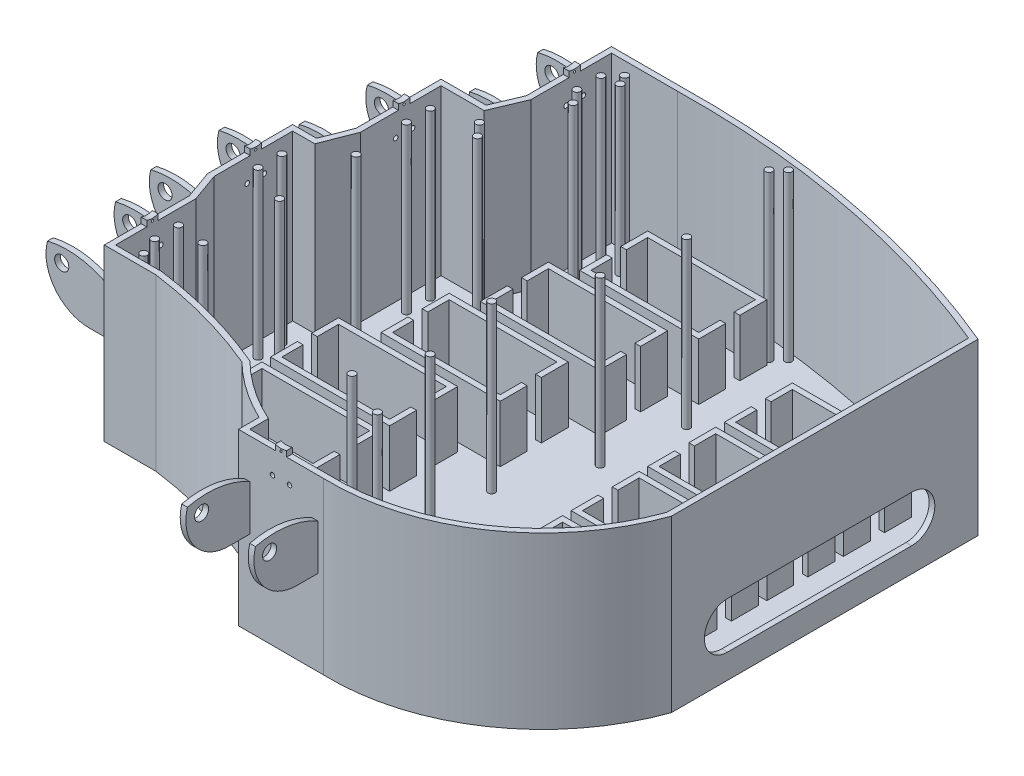
SolidWorks part; units mm, degrees
ref_plane "Front Plane" through (0, 0, 0) normal (0, 0, 1) x (1, 0, 0)
ref_plane "Top Plane" through (0, 0, 0) normal (0, 1, 0) x (1, 0, 0)
ref_plane "Right Plane" through (0, 0, 0) normal (1, 0, 0) x (0, 0, -1)
ref_plane "Palm Side Plane" through (0, 38.1, 0) normal (0, 1, 0) x (1, 0, 0)
ref_plane "Left Side Plane" through (0, 0, 63.5) normal (0, 0, 1) x (1, 0, 0)
ref_plane "Top Side Plane" through (-69.85, 0, 0) normal (1, 0, 0) x (0, 0, -1)
ref_plane "Wrist Plane" through (62.9138, 0, 0) normal (1, 0, 0) x (0, 0, -1)
sketch "Hand Direction Arrow" plane through (0, 38.1, 0) normal (0, 1, 0) x (1, 0, 0)
  line L0 (49.8191, -114.0829) -> (-36.738, -114.0829) construction
  line L1 (-36.738, -114.0829) -> (-22.4792, -131.555) construction
  line L2 (-36.738, -114.0829) -> (-22.4792, -99.8241) construction
sketch "Sketch2" plane through (0, 0, 0) normal (0, 1, 0) x (1, 0, 0)
  line L5 (-69.85, -63.5) -> (69.85, 63.5) construction
  line L6 (-69.85, 63.5) -> (69.85, -63.5) construction
  line L7 (-20.7784, 52.7587) -> (-36.189, 52.7587)
  line L8 (-36.189, 52.7587) -> (-36.189, 33.7087)
  line L9 (-42.9594, -42.4913) -> (-54.5039, -42.4913)
  line L10 (-54.5039, -42.4913) -> (-54.5039, -23.4413)
  line L11 (-54.5039, -23.4413) -> (-56.7676, -17.0913)
  line L12 (-51.4171, 1.9587) -> (-48.9477, 8.3087)
  line L14 (-56.7676, -17.0913) -> (-56.7676, 1.9587)
  line L15 (-56.7676, 1.9587) -> (-51.4171, 1.9587)
  line L16 (-38.8642, 27.3587) -> (-36.189, 33.7087)
  line L19 (15.3118, -63.2103) -> (-3.7382, -63.2103)
  line L20 (-3.7382, -63.2103) -> (-3.7382, -58.593)
  line L21 (61.5724, -31.5884) -> (61.5724, 37.0553)
  line L22 (-48.9477, 8.3087) -> (-48.9477, 27.3587)
  line L23 (-48.9477, 27.3587) -> (-38.8642, 27.3587)
  arc A0 (61.5724, 37.0553) -> (-20.7784, 52.7587) centre (-16.6219, -149.2259) ccw
  arc A2 (-42.9594, -42.4913) -> (-16.4221, -49.7553) centre (-56.8306, -145.2734) cw
  arc A3 (15.3118, -63.2103) -> (61.5724, -31.5884) centre (16.7508, -15.6666) ccw
  arc A5 (-3.7382, -58.593) -> (-16.4221, -49.7553) centre (16.7508, -15.6666) cw
  point P0 (0, 0)
  dimension "D1" = 19.05
  dimension "D2" = 19.05
  dimension "D3" = 19.05
  dimension "D4" = 19.05
  dimension "D5" = 19.05
  dimension "D6" = 6.35
  dimension "D7" = 6.35
extrude "Boss-Extrude1" add sketch "Sketch2" along normal blind 38.1
sketch "Sketch3" plane through (0, 38.1, 0) normal (0, 1, 0) x (1, 0, 0)
  line L5 (-68.58, -62.23) -> (68.58, 62.23) construction
  line L6 (-68.58, 62.23) -> (68.58, -62.23) construction
  line L7 (-20.1932, 51.4997) -> (-34.919, 51.4997)
  line L8 (-34.919, 51.4997) -> (-34.919, 33.4521)
  line L10 (-36.189, 52.7587) -> (-36.189, 33.7087) construction
  line L11 (-54.5039, -23.4413) -> (-54.5039, -42.4913) construction
  line L12 (-42.8744, -41.2213) -> (-53.2339, -41.2213)
  line L13 (-53.2339, -41.2213) -> (-53.2339, -23.2217)
  line L18 (-55.4976, -16.8717) -> (-55.4976, 0.6887)
  line L19 (-55.4976, 0.6887) -> (-50.5484, 0.6887)
  line L22 (-56.7676, 1.9587) -> (-56.7676, -17.0913) construction
  line L23 (-51.4171, 1.9587) -> (-56.7676, 1.9587) construction
  line L24 (-47.6777, 8.0704) -> (-47.6777, 26.0887)
  line L25 (-47.6777, 26.0887) -> (-38.0211, 26.0887)
  line L26 (-48.9477, 27.3587) -> (-48.9477, 8.3087) construction
  line L27 (-38.8642, 27.3587) -> (-48.9477, 27.3587) construction
  line L28 (-38.0211, 26.0887) -> (-34.919, 33.4521)
  line L29 (-36.189, 33.7087) -> (-38.8642, 27.3587) construction
  line L30 (-50.5484, 0.6887) -> (-47.6777, 8.0704)
  line L31 (-54.5039, -42.4913) -> (-42.9594, -42.4913) construction
  line L32 (-53.2339, -23.2217) -> (-55.4976, -16.8717)
  line L33 (-56.7676, -17.0913) -> (-54.5039, -23.4413) construction
  line L34 (-48.9477, 8.3087) -> (-51.4171, 1.9587) construction
  line L35 (15.3312, -61.9403) -> (-2.4682, -61.9403)
  line L36 (-2.4682, -61.9403) -> (-2.4682, -57.7843)
  line L37 (-3.7382, -58.593) -> (-3.7382, -63.2103) construction
  line L38 (-3.7382, -63.2103) -> (15.3118, -63.2103) construction
  line L39 (60.3024, -31.368) -> (60.3024, 36.2091)
  line L40 (61.5724, -31.5884) -> (61.5724, 37.0553) construction
  arc A1 (-20.1932, 51.4997) -> (60.3024, 36.2091) centre (-16.6219, -149.2259) cw
  arc A4 (61.5724, 37.0553) -> (-20.7784, 52.7587) centre (-16.6219, -149.2259) ccw construction
  arc A6 (-15.7053, -48.6798) -> (-2.4682, -57.7843) centre (16.7508, -15.6666) ccw
  arc A7 (15.3118, -63.2103) -> (61.5724, -31.5884) centre (16.7508, -15.6666) ccw construction
  arc A8 (-42.8744, -41.2213) -> (-15.7053, -48.6798) centre (-56.8306, -145.2734) cw
  arc A9 (-16.4221, -49.7553) -> (-42.9594, -42.4913) centre (-56.8306, -145.2734) ccw construction
  arc A11 (15.3118, -63.2103) -> (61.5724, -31.5884) centre (16.7508, -15.6666) ccw construction
  arc A12 (15.3312, -61.9403) -> (60.3024, -31.368) centre (16.7508, -15.6666) ccw
  point P0 (0, 0)
  point P6 (-45.5127, -25.7954)
  point P29 (-45.5127, -25.7954)
  point P52 (-54.0923, 1.9587)
  dimension "D2" = 1.27
  dimension "D3" = 1.27
  dimension "D5" = 1.27
  dimension "D6" = 1.27
  dimension "D8" = 1.27
  dimension "D4" = 1.27
  dimension "D7" = 1.27
  dimension "D9" = 1.27
  dimension "D10" = 1.27
  dimension "D11" = 1.27
  dimension "D12" = 1.27
  dimension "D13" = 1.27
  dimension "D14" = 1.27
  dimension "D15" = 1.27
  dimension "D16" = 1.27
  dimension "D17" = 1.27
extrude "Cut-Extrude1" cut sketch "Sketch3" against normal blind 36.83
sketch "Sketch6" plane through (0, 0, 0) normal (0, 1, 0) x (1, 0, 0)
  line L0 (-38.2959, -32.597) -> (-37.0259, -32.597)
  line L5 (-63.3937, -68.1577) -> (73.7663, 56.3023) construction
  line L6 (-64.5742, 57.9506) -> (72.5858, -66.5094) construction
  line L7 (-12.8959, -37.3595) -> (-37.0259, -37.3595)
  line L8 (-12.8959, -37.3595) -> (-12.8959, -32.597)
  line L9 (-12.8959, -24.6595) -> (-37.0259, -24.6595)
  line L10 (-37.0259, -37.3595) -> (-37.0259, -32.597)
  line L11 (-12.8959, -37.3595) -> (-37.0259, -24.6595) construction
  line L12 (-12.8959, -24.6595) -> (-37.0259, -37.3595) construction
  line L13 (-11.6259, -38.6295) -> (-38.2959, -38.6295)
  line L14 (-11.6259, -38.6295) -> (-11.6259, -32.597)
  line L15 (-11.6259, -23.3895) -> (-38.2959, -23.3895)
  line L16 (-38.2959, -38.6295) -> (-38.2959, -32.597)
  line L17 (-11.6259, -38.6295) -> (-38.2959, -23.3895) construction
  line L18 (-11.6259, -23.3895) -> (-38.2959, -38.6295) construction
  line L19 (-38.2959, -29.422) -> (-37.0259, -29.422)
  line L20 (-38.2959, -29.422) -> (-38.2959, -23.3895)
  line L21 (-37.0259, -29.422) -> (-37.0259, -24.6595)
  line L22 (-12.8959, -32.597) -> (-11.6259, -32.597)
  line L23 (-12.8959, -29.422) -> (-11.6259, -29.422)
  line L24 (-12.8959, -29.422) -> (-12.8959, -24.6595)
  line L25 (-11.6259, -29.422) -> (-11.6259, -23.3895)
  point P0 (5.5042, -5.6391)
  point P6 (-24.9609, -31.0095)
  point P29 (-24.9609, -31.0095)
  dimension "D6" = 1.27
  dimension "D7" = 1.27
  dimension "D9" = 12.7
  dimension "D10" = 24.13
  dimension "D11" = 4.7625
  dimension "D12" = 4.7625
  dimension "D13" = 4.7625
  dimension "D14" = 4.7625
extrude "Boss-Extrude2" add sketch "Sketch6" along normal blind 13.97
sketch "Sketch7" plane through (0, 0, 0) normal (0, 1, 0) x (1, 0, 0)
  line L0 (-38.2959, -15.452) -> (-37.0259, -15.452)
  line L5 (-11.6259, -23.3895) -> (-38.2959, -23.3895) construction
  line L6 (-38.2959, -23.3895) -> (-38.2959, -29.422) construction
  line L7 (-12.8959, -20.2145) -> (-37.0259, -20.2145)
  line L8 (-12.8959, -20.2145) -> (-12.8959, -15.452)
  line L9 (-12.8959, -7.5145) -> (-37.0259, -7.5145)
  line L10 (-37.0259, -20.2145) -> (-37.0259, -15.452)
  line L11 (-12.8959, -20.2145) -> (-37.0259, -7.5145) construction
  line L12 (-12.8959, -7.5145) -> (-37.0259, -20.2145) construction
  line L13 (-11.6259, -21.4845) -> (-38.2959, -21.4845)
  line L14 (-11.6259, -21.4845) -> (-11.6259, -15.452)
  line L15 (-11.6259, -6.2445) -> (-38.2959, -6.2445)
  line L16 (-38.2959, -21.4845) -> (-38.2959, -15.452)
  line L17 (-11.6259, -21.4845) -> (-38.2959, -6.2445) construction
  line L18 (-11.6259, -6.2445) -> (-38.2959, -21.4845) construction
  line L19 (-38.2959, -12.277) -> (-37.0259, -12.277)
  line L20 (-38.2959, -12.277) -> (-38.2959, -6.2445)
  line L21 (-37.0259, -12.277) -> (-37.0259, -7.5145)
  line L22 (-12.8959, -15.452) -> (-11.6259, -15.452)
  line L23 (-12.8959, -12.277) -> (-11.6259, -12.277)
  line L24 (-12.8959, -12.277) -> (-12.8959, -7.5145)
  line L25 (-11.6259, -12.277) -> (-11.6259, -6.2445)
  point P0 (-14.8998, -5.4903)
  point P6 (-24.9609, -13.8645)
  point P29 (-24.9609, -13.8645)
  dimension "D2" = 1.905
  dimension "D3" = 0
  dimension "D6" = 1.27
  dimension "D7" = 1.27
  dimension "D9" = 12.7
  dimension "D10" = 24.13
  dimension "D11" = 4.7625
  dimension "D12" = 4.7625
  dimension "D13" = 4.7625
  dimension "D14" = 4.7625
extrude "Boss-Extrude3" add sketch "Sketch7" along normal blind 13.97
sketch "Sketch15" plane through (0, 0, 0) normal (0, -1, 0) x (1, 0, 0)
  line L0 (-30.6759, -4.868) -> (-29.4059, -4.868)
  line L5 (-11.6259, 6.2445) -> (-38.2959, 6.2445) construction
  line L6 (-38.2959, 6.2445) -> (-38.2959, 12.277) construction
  line L7 (-5.2759, -9.6305) -> (-29.4059, -9.6305)
  line L8 (-5.2759, -9.6305) -> (-5.2759, -4.868)
  line L9 (-5.2759, 3.0695) -> (-29.4059, 3.0695)
  line L10 (-29.4059, -9.6305) -> (-29.4059, -4.868)
  line L11 (-5.2759, -9.6305) -> (-29.4059, 3.0695) construction
  line L12 (-5.2759, 3.0695) -> (-29.4059, -9.6305) construction
  line L13 (-4.0059, -10.9005) -> (-30.6759, -10.9005)
  line L14 (-4.0059, -10.9005) -> (-4.0059, -4.868)
  line L15 (-4.0059, 4.3395) -> (-30.6759, 4.3395)
  line L16 (-30.6759, -10.9005) -> (-30.6759, -4.868)
  line L17 (-4.0059, -10.9005) -> (-30.6759, 4.3395) construction
  line L18 (-4.0059, 4.3395) -> (-30.6759, -10.9005) construction
  line L19 (-30.6759, -1.693) -> (-29.4059, -1.693)
  line L20 (-30.6759, -1.693) -> (-30.6759, 4.3395)
  line L21 (-29.4059, -1.693) -> (-29.4059, 3.0695)
  line L22 (-5.2759, -4.868) -> (-4.0059, -4.868)
  line L23 (-5.2759, -1.693) -> (-4.0059, -1.693)
  line L24 (-5.2759, -1.693) -> (-5.2759, 3.0695)
  line L25 (-4.0059, -1.693) -> (-4.0059, 4.3395)
  point P0 (-6.5637, 8.998)
  point P6 (-17.3409, -3.2805)
  point P29 (-17.3409, -3.2805)
  dimension "D2" = 1.905
  dimension "D3" = 7.62
  dimension "D6" = 1.27
  dimension "D7" = 1.27
  dimension "D9" = 12.7
  dimension "D10" = 24.13
  dimension "D11" = 4.7625
  dimension "D12" = 4.7625
  dimension "D13" = 4.7625
  dimension "D14" = 4.7625
extrude "Boss-Extrude4" add sketch "Sketch15" against normal blind 13.97
sketch "Sketch16" plane through (0, 0, 0) normal (0, -1, 0) x (1, 0, 0)
  line L0 (-25.5959, -22.013) -> (-24.3259, -22.013)
  line L5 (-30.6759, -10.9005) -> (-4.0059, -10.9005) construction
  line L6 (-30.6759, -4.868) -> (-30.6759, -10.9005) construction
  line L7 (-0.1959, -26.7755) -> (-24.3259, -26.7755)
  line L8 (-0.1959, -26.7755) -> (-0.1959, -22.013)
  line L9 (-0.1959, -14.0755) -> (-24.3259, -14.0755)
  line L10 (-24.3259, -26.7755) -> (-24.3259, -22.013)
  line L11 (-0.1959, -26.7755) -> (-24.3259, -14.0755) construction
  line L12 (-0.1959, -14.0755) -> (-24.3259, -26.7755) construction
  line L13 (1.0741, -28.0455) -> (-25.5959, -28.0455)
  line L14 (1.0741, -28.0455) -> (1.0741, -22.013)
  line L15 (1.0741, -12.8055) -> (-25.5959, -12.8055)
  line L16 (-25.5959, -28.0455) -> (-25.5959, -22.013)
  line L17 (1.0741, -28.0455) -> (-25.5959, -12.8055) construction
  line L18 (1.0741, -12.8055) -> (-25.5959, -28.0455) construction
  line L19 (-25.5959, -18.838) -> (-24.3259, -18.838)
  line L20 (-25.5959, -18.838) -> (-25.5959, -12.8055)
  line L21 (-24.3259, -18.838) -> (-24.3259, -14.0755)
  line L22 (-0.1959, -22.013) -> (1.0741, -22.013)
  line L23 (-0.1959, -18.838) -> (1.0741, -18.838)
  line L24 (-0.1959, -18.838) -> (-0.1959, -14.0755)
  line L25 (1.0741, -18.838) -> (1.0741, -12.8055)
  point P0 (1.9027, -6.9539)
  point P6 (-12.2609, -20.4255)
  point P29 (-12.2609, -20.4255)
  dimension "D2" = 1.905
  dimension "D3" = 5.08
  dimension "D6" = 1.27
  dimension "D7" = 1.27
  dimension "D9" = 12.7
  dimension "D10" = 24.13
  dimension "D11" = 4.7625
  dimension "D12" = 4.7625
  dimension "D13" = 4.7625
  dimension "D14" = 4.7625
extrude "Boss-Extrude5" add sketch "Sketch16" against normal blind 13.97
sketch "Sketch17" plane through (0, 0, 0) normal (0, -1, 0) x (1, 0, 0)
  line L0 (-20.5159, -39.158) -> (-19.2459, -39.158)
  line L5 (-25.5959, -28.0455) -> (1.0741, -28.0455) construction
  line L6 (-25.5959, -22.013) -> (-25.5959, -28.0455) construction
  line L7 (4.8841, -43.9205) -> (-19.2459, -43.9205)
  line L8 (4.8841, -43.9205) -> (4.8841, -39.158)
  line L9 (4.8841, -31.2205) -> (-19.2459, -31.2205)
  line L10 (-19.2459, -43.9205) -> (-19.2459, -39.158)
  line L11 (4.8841, -43.9205) -> (-19.2459, -31.2205) construction
  line L12 (4.8841, -31.2205) -> (-19.2459, -43.9205) construction
  line L13 (6.1541, -45.1905) -> (-20.5159, -45.1905)
  line L14 (6.1541, -45.1905) -> (6.1541, -39.158)
  line L15 (6.1541, -29.9505) -> (-20.5159, -29.9505)
  line L16 (-20.5159, -45.1905) -> (-20.5159, -39.158)
  line L17 (6.1541, -45.1905) -> (-20.5159, -29.9505) construction
  line L18 (6.1541, -29.9505) -> (-20.5159, -45.1905) construction
  line L19 (-20.5159, -35.983) -> (-19.2459, -35.983)
  line L20 (-20.5159, -35.983) -> (-20.5159, -29.9505)
  line L21 (-19.2459, -35.983) -> (-19.2459, -31.2205)
  line L22 (4.8841, -39.158) -> (6.1541, -39.158)
  line L23 (4.8841, -35.983) -> (6.1541, -35.983)
  line L24 (4.8841, -35.983) -> (4.8841, -31.2205)
  line L25 (6.1541, -35.983) -> (6.1541, -29.9505)
  point P0 (6.1079, -24.4951)
  point P6 (-7.1809, -37.5705)
  point P29 (-7.1809, -37.5705)
  dimension "D2" = 1.905
  dimension "D3" = 5.08
  dimension "D6" = 1.27
  dimension "D7" = 1.27
  dimension "D9" = 12.7
  dimension "D10" = 24.13
  dimension "D11" = 4.7625
  dimension "D12" = 4.7625
  dimension "D13" = 4.7625
  dimension "D14" = 4.7625
extrude "Boss-Extrude6" add sketch "Sketch17" against normal blind 13.97
sketch "Sketch18" plane through (0, 0, 0) normal (0, -1, 0) x (1, 0, 0)
  line L0 (14.981, 42.6949) -> (16.251, 42.6949)
  line L7 (40.381, 37.9324) -> (16.251, 37.9324)
  line L8 (40.381, 37.9324) -> (40.381, 42.6949)
  line L9 (40.381, 50.6324) -> (16.251, 50.6324)
  line L10 (16.251, 37.9324) -> (16.251, 42.6949)
  line L11 (40.381, 37.9324) -> (16.251, 50.6324) construction
  line L12 (40.381, 50.6324) -> (16.251, 37.9324) construction
  line L13 (41.651, 36.6624) -> (14.981, 36.6624)
  line L14 (41.651, 36.6624) -> (41.651, 42.6949)
  line L15 (41.651, 51.9024) -> (14.981, 51.9024)
  line L16 (14.981, 36.6624) -> (14.981, 42.6949)
  line L17 (41.651, 36.6624) -> (14.981, 51.9024) construction
  line L18 (41.651, 51.9024) -> (14.981, 36.6624) construction
  line L19 (14.981, 45.8699) -> (16.251, 45.8699)
  line L20 (14.981, 45.8699) -> (14.981, 51.9024)
  line L21 (16.251, 45.8699) -> (16.251, 50.6324)
  line L22 (40.381, 42.6949) -> (41.651, 42.6949)
  line L23 (40.381, 45.8699) -> (41.651, 45.8699)
  line L24 (40.381, 45.8699) -> (40.381, 50.6324)
  line L25 (41.651, 45.8699) -> (41.651, 51.9024)
  point P0 (43.5107, 54.1626)
  point P6 (28.316, 44.2824)
  point P29 (28.316, 44.2824)
  dimension "D6" = 1.27
  dimension "D7" = 1.27
  dimension "D9" = 12.7
  dimension "D10" = 24.13
  dimension "D11" = 4.7625
  dimension "D12" = 4.7625
  dimension "D13" = 4.7625
  dimension "D14" = 4.7625
extrude "Boss-Extrude7" add sketch "Sketch18" against normal blind 13.97
sketch "Sketch19" plane through (0, 0, 0) normal (0, -1, 0) x (1, 0, 0)
  line L0 (25.141, 25.5499) -> (26.411, 25.5499)
  line L5 (14.981, 36.6624) -> (41.651, 36.6624) construction
  line L6 (14.981, 42.6949) -> (14.981, 36.6624) construction
  line L7 (50.541, 20.7874) -> (26.411, 20.7874)
  line L8 (50.541, 20.7874) -> (50.541, 25.5499)
  line L9 (50.541, 33.4874) -> (26.411, 33.4874)
  line L10 (26.411, 20.7874) -> (26.411, 25.5499)
  line L11 (50.541, 20.7874) -> (26.411, 33.4874) construction
  line L12 (50.541, 33.4874) -> (26.411, 20.7874) construction
  line L13 (51.811, 19.5174) -> (25.141, 19.5174)
  line L14 (51.811, 19.5174) -> (51.811, 25.5499)
  line L15 (51.811, 34.7574) -> (25.141, 34.7574)
  line L16 (25.141, 19.5174) -> (25.141, 25.5499)
  line L17 (51.811, 19.5174) -> (25.141, 34.7574) construction
  line L18 (51.811, 34.7574) -> (25.141, 19.5174) construction
  line L19 (25.141, 28.7249) -> (26.411, 28.7249)
  line L20 (25.141, 28.7249) -> (25.141, 34.7574)
  line L21 (26.411, 28.7249) -> (26.411, 33.4874)
  line L22 (50.541, 25.5499) -> (51.811, 25.5499)
  line L23 (50.541, 28.7249) -> (51.811, 28.7249)
  line L24 (50.541, 28.7249) -> (50.541, 33.4874)
  line L25 (51.811, 28.7249) -> (51.811, 34.7574)
  point P0 (52.4146, 37.8023)
  point P6 (38.476, 27.1374)
  point P29 (38.476, 27.1374)
  dimension "D2" = 1.905
  dimension "D3" = 10.16
  dimension "D6" = 1.27
  dimension "D7" = 1.27
  dimension "D9" = 12.7
  dimension "D10" = 24.13
  dimension "D11" = 4.7625
  dimension "D12" = 4.7625
  dimension "D13" = 4.7625
  dimension "D14" = 4.7625
extrude "Boss-Extrude8" add sketch "Sketch19" against normal blind 13.97
sketch "Sketch20" plane through (0, 0, 0) normal (0, -1, 0) x (1, 0, 0)
  line L0 (25.141, 8.4049) -> (26.411, 8.4049)
  line L5 (25.141, 25.5499) -> (25.141, 19.5174) construction
  line L6 (25.141, 19.5174) -> (51.811, 19.5174) construction
  line L7 (50.541, 3.6424) -> (26.411, 3.6424)
  line L8 (50.541, 3.6424) -> (50.541, 8.4049)
  line L9 (50.541, 16.3424) -> (26.411, 16.3424)
  line L10 (26.411, 3.6424) -> (26.411, 8.4049)
  line L11 (50.541, 3.6424) -> (26.411, 16.3424) construction
  line L12 (50.541, 16.3424) -> (26.411, 3.6424) construction
  line L13 (51.811, 2.3724) -> (25.141, 2.3724)
  line L14 (51.811, 2.3724) -> (51.811, 8.4049)
  line L15 (51.811, 17.6124) -> (25.141, 17.6124)
  line L16 (25.141, 2.3724) -> (25.141, 8.4049)
  line L17 (51.811, 2.3724) -> (25.141, 17.6124) construction
  line L18 (51.811, 17.6124) -> (25.141, 2.3724) construction
  line L19 (25.141, 11.5799) -> (26.411, 11.5799)
  line L20 (25.141, 11.5799) -> (25.141, 17.6124)
  line L21 (26.411, 11.5799) -> (26.411, 16.3424)
  line L22 (50.541, 8.4049) -> (51.811, 8.4049)
  line L23 (50.541, 11.5799) -> (51.811, 11.5799)
  line L24 (50.541, 11.5799) -> (50.541, 16.3424)
  line L25 (51.811, 11.5799) -> (51.811, 17.6124)
  point P0 (54.8865, 20.8211)
  point P6 (38.476, 9.9924)
  point P29 (38.476, 9.9924)
  dimension "D2" = 0
  dimension "D3" = 1.905
  dimension "D6" = 1.27
  dimension "D7" = 1.27
  dimension "D9" = 12.7
  dimension "D10" = 24.13
  dimension "D11" = 4.7625
  dimension "D12" = 4.7625
  dimension "D13" = 4.7625
  dimension "D14" = 4.7625
extrude "Boss-Extrude9" add sketch "Sketch20" against normal blind 13.97
sketch "Sketch21" plane through (0, 0, 0) normal (0, -1, 0) x (1, 0, 0)
  line L0 (25.141, -8.7401) -> (26.411, -8.7401)
  line L5 (25.141, 2.3724) -> (51.811, 2.3724) construction
  line L6 (25.141, 8.4049) -> (25.141, 2.3724) construction
  line L7 (50.541, -13.5026) -> (26.411, -13.5026)
  line L8 (50.541, -13.5026) -> (50.541, -8.7401)
  line L9 (50.541, -0.8026) -> (26.411, -0.8026)
  line L10 (26.411, -13.5026) -> (26.411, -8.7401)
  line L11 (50.541, -13.5026) -> (26.411, -0.8026) construction
  line L12 (50.541, -0.8026) -> (26.411, -13.5026) construction
  line L13 (51.811, -14.7726) -> (25.141, -14.7726)
  line L14 (51.811, -14.7726) -> (51.811, -8.7401)
  line L15 (51.811, 0.4674) -> (25.141, 0.4674)
  line L16 (25.141, -14.7726) -> (25.141, -8.7401)
  line L17 (51.811, -14.7726) -> (25.141, 0.4674) construction
  line L18 (51.811, 0.4674) -> (25.141, -14.7726) construction
  line L19 (25.141, -5.5651) -> (26.411, -5.5651)
  line L20 (25.141, -5.5651) -> (25.141, 0.4674)
  line L21 (26.411, -5.5651) -> (26.411, -0.8026)
  line L22 (50.541, -8.7401) -> (51.811, -8.7401)
  line L23 (50.541, -5.5651) -> (51.811, -5.5651)
  line L24 (50.541, -5.5651) -> (50.541, -0.8026)
  line L25 (51.811, -5.5651) -> (51.811, 0.4674)
  point P0 (52.1156, 3.8173)
  point P6 (38.476, -7.1526)
  point P29 (38.476, -7.1526)
  dimension "D2" = 1.905
  dimension "D3" = 0
  dimension "D6" = 1.27
  dimension "D7" = 1.27
  dimension "D9" = 12.7
  dimension "D10" = 24.13
  dimension "D11" = 4.7625
  dimension "D12" = 4.7625
  dimension "D13" = 4.7625
  dimension "D14" = 4.7625
extrude "Boss-Extrude10" add sketch "Sketch21" against normal blind 13.97
sketch "Sketch22" plane through (0, 0, 0) normal (0, -1, 0) x (1, 0, 0)
  line L0 (25.141, -25.8851) -> (26.411, -25.8851)
  line L5 (25.141, -14.7726) -> (51.811, -14.7726) construction
  line L6 (25.141, -8.7401) -> (25.141, -14.7726) construction
  line L7 (50.541, -30.6476) -> (26.411, -30.6476)
  line L8 (50.541, -30.6476) -> (50.541, -25.8851)
  line L9 (50.541, -17.9476) -> (26.411, -17.9476)
  line L10 (26.411, -30.6476) -> (26.411, -25.8851)
  line L11 (50.541, -30.6476) -> (26.411, -17.9476) construction
  line L12 (50.541, -17.9476) -> (26.411, -30.6476) construction
  line L13 (51.811, -31.9176) -> (25.141, -31.9176)
  line L14 (51.811, -31.9176) -> (51.811, -25.8851)
  line L15 (51.811, -16.6776) -> (25.141, -16.6776)
  line L16 (25.141, -31.9176) -> (25.141, -25.8851)
  line L17 (51.811, -31.9176) -> (25.141, -16.6776) construction
  line L18 (51.811, -16.6776) -> (25.141, -31.9176) construction
  line L19 (25.141, -22.7101) -> (26.411, -22.7101)
  line L20 (25.141, -22.7101) -> (25.141, -16.6776)
  line L21 (26.411, -22.7101) -> (26.411, -17.9476)
  line L22 (50.541, -25.8851) -> (51.811, -25.8851)
  line L23 (50.541, -22.7101) -> (51.811, -22.7101)
  line L24 (50.541, -22.7101) -> (50.541, -17.9476)
  line L25 (51.811, -22.7101) -> (51.811, -16.6776)
  point P0 (57.6091, -14.277)
  point P6 (38.476, -24.2976)
  point P29 (38.476, -24.2976)
  dimension "D2" = 1.905
  dimension "D3" = 0
  dimension "D6" = 1.27
  dimension "D7" = 1.27
  dimension "D9" = 12.7
  dimension "D10" = 24.13
  dimension "D11" = 4.7625
  dimension "D12" = 4.7625
  dimension "D13" = 4.7625
  dimension "D14" = 4.7625
extrude "Boss-Extrude11" add sketch "Sketch22" against normal blind 13.97
sketch "Sketch25" plane through (0, 0, 63.5) normal (0, 0, 1) x (1, 0, 0)
  line L1 (49.8191, 38.1) -> (-36.738, 38.1) construction
  line L6 (-3.7382, 38.1) -> (-3.7382, 0) construction
  line L7 (15.3118, 38.1) -> (15.3118, 0) construction
  circle A0 centre (7.6918, 33.02) radius 0.508
  circle A1 centre (3.8818, 33.02) radius 0.508
  dimension "D3" = 7.62
  dimension "D1" = 5.08
  dimension "D2" = 5.08
  dimension "D4" = 7.62
extrude "Thumb Holes" cut sketch "Sketch25" against normal blind 12.7
sketch "Sketch31" plane through (-69.85, 0, 0) normal (1, 0, 0) x (0, 0, -1)
  line L0 (-23.4413, 38.1) -> (-23.4413, 0) construction
  line L1 (-23.4413, 38.1) -> (-42.4913, 38.1) construction
  line L2 (-42.4913, 38.1) -> (-42.4913, 0) construction
  circle A0 centre (-31.0613, 33.02) radius 0.508
  circle A1 centre (-34.8713, 33.02) radius 0.508
  dimension "D1" = 7.62
  dimension "D2" = 5.08
  dimension "D3" = 5.08
  dimension "D4" = 7.62
extrude "Index Finger Holes" cut sketch "Sketch31" along normal blind 17.018
sketch "Sketch32" plane through (-69.85, 0, 0) normal (1, 0, 0) x (0, 0, -1)
  line L0 (1.9587, 38.1) -> (1.9587, 0) construction
  line L1 (-17.0913, 38.1) -> (-17.0913, 0) construction
  line L2 (1.9587, 38.1) -> (-17.0913, 38.1) construction
  circle A0 centre (-9.4713, 33.02) radius 0.508
  circle A1 centre (-5.6613, 33.02) radius 0.508
  dimension "D1" = 7.62
  dimension "D2" = 7.62
  dimension "D3" = 5.08
  dimension "D4" = 5.08
extrude "Middle Finger Holes" cut sketch "Sketch32" along normal blind 15.24
sketch "Sketch33" plane through (-69.85, 0, 0) normal (1, 0, 0) x (0, 0, -1)
  line L0 (27.3587, 38.1) -> (27.3587, 0) construction
  line L1 (27.3587, 38.1) -> (8.3087, 38.1) construction
  line L2 (8.3087, 38.1) -> (8.3087, 0) construction
  circle A0 centre (15.9287, 33.02) radius 0.508
  circle A1 centre (19.7387, 33.02) radius 0.508
  dimension "D1" = 7.62
  dimension "D2" = 5.08
  dimension "D3" = 5.08
  dimension "D4" = 7.62
extrude "Ring Finger Holes" cut sketch "Sketch33" along normal blind 22.86
sketch "Sketch34" plane through (-69.85, 0, 0) normal (1, 0, 0) x (0, 0, -1)
  line L0 (52.7587, 38.1) -> (33.7087, 38.1) construction
  line L1 (52.8014, 0) -> (52.8014, 38.1) construction
  line L2 (33.7087, 38.1) -> (33.7087, 0) construction
  circle A0 centre (41.3287, 33.02) radius 0.508
  circle A1 centre (45.1814, 33.02) radius 0.508
  dimension "D1" = 5.08
  dimension "D2" = 7.62
  dimension "D3" = 7.62
  dimension "D4" = 5.08
extrude "Pinky Finger Holes" cut sketch "Sketch34" along normal blind 35.56
sketch "Sketch26" plane through (0, 38.1, 0) normal (0, 1, 0) x (1, 0, 0)
  line L0 (-1.8504, -40.4696) -> (-48.4714, -40.4696) construction
  line L1 (8.3049, 24.2976) -> (8.3049, 48.6758) construction
  line L2 (6.0975, 7.1526) -> (6.0975, 46.5196) construction
  line L3 (-1.0566, -9.9924) -> (-1.0566, -39.6758) construction
  line L4 (-53.2339, -23.2217) -> (-53.2339, -41.2213) construction
  line L5 (-37.0259, -15.452) -> (-38.2959, -15.452) construction
  line L6 (14.981, -45.8699) -> (16.251, -45.8699) construction
  line L7 (25.141, -28.7249) -> (26.411, -28.7249) construction
  line L8 (25.141, -11.5799) -> (26.411, -11.5799) construction
  line L9 (25.141, 5.5651) -> (26.411, 5.5651) construction
  line L10 (25.141, 22.7101) -> (26.411, 22.7101) construction
  line L11 (-30.6759, 1.693) -> (-29.4059, 1.693) construction
  line L12 (-25.5959, 18.838) -> (-24.3259, 18.838) construction
  line L13 (-20.5159, 35.983) -> (-19.2459, 35.983) construction
  line L14 (5.3037, 47.3134) -> (-28.0099, 47.3134) construction
  line L15 (7.5112, 49.4695) -> (-29.1533, 49.4695) construction
  line L16 (-53.2339, -23.2217) -> (-53.2339, -41.2213) construction
  line L17 (-55.4976, 0.6887) -> (-55.4976, -16.8717) construction
  line L18 (-47.6777, 26.0887) -> (-47.6777, 8.0704) construction
  line L19 (-47.6777, 26.0887) -> (-47.6777, 8.0704) construction
  line L20 (-34.919, 51.4997) -> (-34.919, 33.4521) construction
  line L21 (-34.919, 51.4997) -> (-34.919, 33.4521) construction
  line L22 (-37.0259, -32.597) -> (-38.2959, -32.597) construction
  line L23 (-49.2652, -39.6758) -> (-49.2652, -35.6333) construction
  circle A0 centre (8.4538, -44.2824) radius 0.7937
  circle A1 centre (3.1198, -27.1374) radius 0.7937
  circle A2 centre (-0.2629, -9.9924) radius 0.7937
  circle A3 centre (6.8912, 7.1526) radius 0.7938
  circle A4 centre (9.0987, 24.2976) radius 0.7937
  circle A5 centre (-1.8504, -39.6758) radius 0.7938
  circle A6 centre (7.5112, 48.6758) radius 0.7938
  circle A7 centre (5.3037, 46.5196) radius 0.7938
  circle A8 centre (-48.4714, -39.6758) radius 0.7937
  circle A9 centre (-52.3226, -10.2333) radius 0.7937
  circle A10 centre (-52.3226, -4.8993) radius 0.7937
  circle A11 centre (-43.8931, -13.8645) radius 0.7937
  circle A12 centre (-43.8931, 3.2805) radius 0.7937
  circle A13 centre (-33.8741, 20.4255) radius 0.7937
  circle A14 centre (-44.5027, 15.1667) radius 0.7937
  circle A15 centre (-29.6038, 37.5705) radius 0.7937
  circle A16 centre (-36.3066, 23.2954) radius 0.7937
  circle A17 centre (-44.5027, 20.5007) radius 0.7937
  circle A18 centre (-28.0099, 46.5196) radius 0.7937
  circle A19 centre (-29.1533, 48.6758) radius 0.7938
  circle A20 centre (-31.744, 40.5667) radius 0.7937
  circle A21 centre (-31.744, 45.9434) radius 0.7937
  circle A22 centre (-50.0589, -35.6333) radius 0.7937
  circle A23 centre (-50.0589, -30.2993) radius 0.7937
  circle A24 centre (-43.8931, -31.0095) radius 0.7937
  dimension "D6" = 0.254
  dimension "D7" = 0.254
  dimension "D14" = 1.5875
  dimension "D15" = 1.5875
  dimension "D16" = 1.5875
  dimension "D17" = 1.5875
  dimension "D18" = 1.5875
  dimension "D19" = 1.5875
  dimension "D20" = 1.5875
  dimension "D21" = 1.5875
  dimension "D22" = 1.5875
  dimension "D23" = 1.5875
  dimension "D24" = 1.5875
  dimension "D25" = 1.5875
  dimension "D26" = 1.5875
  dimension "D27" = 1.5875
  dimension "D28" = 1.5875
  dimension "D29" = 1.5875
  dimension "D30" = 1.5875
  dimension "D31" = 1.5875
  dimension "D32" = 1.5875
  dimension "D33" = 1.5875
  dimension "D34" = 1.5875
  dimension "D35" = 1.5875
  dimension "D41" = 0.254
  dimension "D52" = 1.5875
  dimension "D42" = 1.5875
  dimension "D53" = 1.5875
  dimension "D1" = 1.5875
  dimension "D2" = 1.5875
  dimension "D3" = 1.5875
  dimension "D4" = 1.5875
  dimension "D5" = 1.5875
  dimension "D8" = 1.5875
  dimension "D9" = 1.5875
  dimension "D10" = 1.5875
  dimension "D11" = 1.5875
  dimension "D12" = 0.254
  dimension "D13" = 0.254
  dimension "D36" = 0.254
  dimension "D37" = 0.254
  dimension "D38" = 0.254
  dimension "D39" = 0.254
  dimension "D40" = 0.254
  dimension "D43" = 3.175
  dimension "D44" = 3.175
  dimension "D45" = 3.175
  dimension "D46" = 3.175
  dimension "D47" = 3.175
  dimension "D48" = 3.175
  dimension "D49" = 3.175
  dimension "D50" = 3.175
  dimension "D51" = 1.5875
extrude "Guide Poles" add sketch "Sketch26" against normal blind 36.83
ref_plane "Pinky Attachment Plane" through (0, 0, -52.7587) normal (0, 0, -1) x (-1, 0, 0)
ref_plane "Ring Attachment Plane" through (0, 0, -27.3587) normal (0, 0, -1) x (-1, 0, 0)
ref_plane "Middle Attachment Plane" through (0, 0, -1.9587) normal (0, 0, -1) x (-1, 0, 0)
ref_plane "Pointer Attachment Plane" through (0, 0, 23.4413) normal (0, 0, -1) x (-1, 0, 0)
ref_plane "Thumb Attachment Plane" through (-3.7382, 0, 0) normal (-1, 0, 0) x (0, 0, 1)
sketch "Sketch35" plane through (0, 0, -52.7587) normal (0, 0, -1) x (-1, 0, 0)
  line L1 (36.189, 38.1) -> (36.189, 0) construction
  line L2 (38.8642, 38.1) -> (48.9477, 38.1) construction
  line L3 (36.189, 19.05) -> (40.634, 19.05)
  line L4 (40.634, 38.1) -> (40.634, 19.05) construction
  line L5 (36.189, 29.21) -> (36.189, 19.05)
  line L6 (36.189, 38.1) -> (36.189, 0) construction
  circle A1 centre (46.984, 28.575) radius 1.5875
  arc A2 (50.159, 31.242) -> (40.634, 19.05) centre (40.8478, 28.6996) cw
  arc A3 (50.159, 31.242) -> (36.189, 29.21) centre (45.7208, 12.7162) ccw
  point P0 (49.5161, 31.242)
  point P15 (36.189, 30.3611)
  dimension "D1" = 10.795
  dimension "D2" = 4.445
  dimension "D3" = 8.89
  dimension "D4" = 6.858
  dimension "D5" = 13.97
extrude "Pinky Attachment" add sketch "Sketch35" against normal blind 19.05
sketch "Sketch36" plane through (0, 0, -27.3587) normal (0, 0, -1) x (-1, 0, 0)
  line L0 (51.4171, 38.1) -> (56.7676, 38.1) construction
  line L3 (48.9477, 29.21) -> (48.9477, 19.05)
  line L4 (48.9477, 38.1) -> (48.9477, 0) construction
  line L5 (48.9477, 19.05) -> (53.3927, 19.05)
  line L6 (53.3927, 38.1) -> (53.3927, 19.05) construction
  line L7 (48.9477, 38.1) -> (48.9477, 0) construction
  arc A0 (62.9177, 31.242) -> (53.3927, 19.05) centre (53.6065, 28.6996) cw
  circle A1 centre (59.7427, 28.7074) radius 1.5875
  arc A2 (48.9477, 29.21) -> (62.9177, 31.242) centre (58.4796, 12.7162) cw
  dimension "D1" = 4.445
  dimension "D2" = 10.795
  dimension "D3" = 13.97
  dimension "D4" = 6.858
extrude "Ring Attachment" add sketch "Sketch36" against normal blind 19.05
sketch "Sketch37" plane through (0, 0, -1.9587) normal (0, 0, -1) x (-1, 0, 0)
  line L0 (51.4171, 38.1) -> (56.7676, 38.1) construction
  line L2 (56.7676, 29.21) -> (56.7676, 19.05)
  line L3 (56.7676, 38.1) -> (56.7676, 0) construction
  line L4 (56.7676, 19.05) -> (61.2126, 19.05)
  line L7 (61.2126, 38.1) -> (61.2126, 19.05) construction
  arc A2 (70.7376, 31.242) -> (61.2126, 19.05) centre (61.4264, 28.6996) cw
  circle A3 centre (67.5626, 28.575) radius 1.5875
  arc A4 (56.7676, 29.21) -> (70.7376, 31.242) centre (66.2994, 12.7162) cw
  dimension "D1" = 4.445
  dimension "D3" = 13.97
  dimension "D2" = 10.795
  dimension "D5" = 6.858
extrude "Middle Attachment" add sketch "Sketch37" against normal blind 19.05
sketch "Sketch38" plane through (0, 0, 23.4413) normal (0, 0, -1) x (-1, 0, 0)
  line L0 (51.4171, 38.1) -> (56.7676, 38.1) construction
  line L3 (58.9489, 38.1) -> (58.9489, 19.05) construction
  line L4 (58.9489, 19.05) -> (54.5039, 19.05)
  line L5 (54.5039, 38.1) -> (54.5039, 0) construction
  line L6 (54.5039, 38.1) -> (54.5039, 0) construction
  line L7 (54.5039, 29.21) -> (54.5039, 19.05)
  arc A2 (68.4739, 31.242) -> (58.9489, 19.05) centre (59.1628, 28.6996) cw
  circle A3 centre (65.2989, 28.575) radius 1.5875
  arc A4 (54.5039, 29.21) -> (68.4739, 31.242) centre (64.0358, 12.7162) cw
  dimension "D3" = 13.97
  dimension "D1" = 4.445
  dimension "D2" = 10.795
  dimension "D4" = 6.858
extrude "Pointer Attachment" add sketch "Sketch38" against normal blind 19.05
sketch "Sketch39" plane through (-3.7382, 0, 0) normal (-1, 0, 0) x (0, 0, 1)
  line L0 (63.2103, 38.1) -> (63.2103, 0) construction
  line L4 (63.2103, 19.05) -> (67.6553, 19.05)
  line L5 (63.2103, 38.1) -> (63.2103, 0) construction
  line L6 (63.2103, 29.21) -> (63.2103, 19.05)
  line L7 (67.6553, 38.1) -> (67.6553, 19.05) construction
  arc A0 (77.1803, 31.242) -> (67.6553, 19.05) centre (67.8692, 28.6996) cw
  circle A1 centre (74.0053, 28.575) radius 1.5875
  arc A2 (63.2103, 29.21) -> (77.1803, 31.242) centre (72.7422, 12.7162) cw
  point P13 (63.2321, 28.575)
  point P14 (63.2103, 29.4661)
  dimension "D1" = 4.445
  dimension "D3" = 13.97
  dimension "D2" = 10.795
  dimension "D4" = 6.858
extrude "Thumb Attachment" add sketch "Sketch39" against normal blind 19.05
sketch "Sketch40" plane through (0, 38.1, 0) normal (0, 1, 0) x (1, 0, 0)
  line L0 (-56.7676, 1.9587) -> (-56.7676, -17.0913) construction
  line L1 (-1.1982, -63.2103) -> (12.7718, -63.2103)
  line L2 (-1.1982, -63.2103) -> (-1.1982, -78.4786)
  line L4 (12.7718, -63.2103) -> (12.7718, -78.5359)
  line L5 (-2.4682, -63.2103) -> (-2.4682, -78.4786)
  line L6 (-2.4682, -78.4786) -> (-1.1982, -78.4786)
  line L7 (-6.4204, -63.2103) -> (-2.4682, -63.2103)
  line L8 (15.3118, -63.2103) -> (14.0418, -63.2103)
  line L9 (14.0418, -63.2103) -> (14.0418, -78.5359)
  line L10 (14.0418, -78.5359) -> (12.7718, -78.5359)
  line L11 (-54.5039, -42.4913) -> (-54.5039, -41.2213)
  line L13 (-54.5039, -41.2213) -> (-69.4507, -41.2213)
  line L15 (-69.4507, -41.2213) -> (-69.4507, -39.9513)
  line L16 (-69.4507, -39.9513) -> (-54.5039, -39.9513)
  line L17 (-54.5039, -39.9513) -> (-54.5039, -25.9813)
  line L18 (-54.5039, -25.9813) -> (-69.5228, -25.9813)
  line L19 (-69.5228, -25.9813) -> (-69.5228, -24.7113)
  line L20 (-69.5228, -24.7113) -> (-54.5039, -24.7113)
  line L21 (-54.5039, -24.7113) -> (-54.5039, -23.4413)
  line L22 (-56.7676, -17.0913) -> (-56.7676, -15.8213)
  line L24 (-56.7676, -15.8213) -> (-71.425, -15.8213)
  line L25 (-71.425, -15.8213) -> (-71.425, -14.5513)
  line L26 (-71.425, -14.5513) -> (-56.7676, -14.5513)
  line L27 (-56.7676, -14.5513) -> (-56.7676, -0.5813)
  line L28 (-56.7676, -0.5813) -> (-71.3004, -0.5813)
  line L29 (-71.3004, -0.5813) -> (-71.3004, 0.6887)
  line L31 (-56.7676, 0.6887) -> (-56.7676, 1.9587)
  line L32 (-71.3004, 0.6887) -> (-56.7676, 0.6887)
  line L33 (-47.6777, 26.0887) -> (-47.6777, 8.0704) construction
  line L34 (-48.9477, 8.3087) -> (-48.9477, 9.5787)
  line L36 (-48.9477, 9.5787) -> (-63.8166, 9.5787)
  line L37 (-63.8166, 9.5787) -> (-63.8166, 10.8487)
  line L38 (-63.8166, 10.8487) -> (-48.9477, 10.8487)
  line L39 (-48.9477, 10.8487) -> (-48.9477, 24.8187)
  line L40 (-48.9477, 24.8187) -> (-63.8713, 24.8187)
  line L41 (-63.8713, 24.8187) -> (-63.8713, 26.0887)
  line L42 (-63.8713, 26.0887) -> (-48.9477, 26.0887)
  line L43 (-48.9477, 26.0887) -> (-48.9477, 27.3587)
  line L44 (-36.189, 33.7087) -> (-36.189, 34.9787)
  line L45 (-2.4682, -61.9403) -> (15.3312, -61.9403) construction
  line L46 (-36.189, 34.9787) -> (-51.8787, 34.9787)
  line L47 (-51.8787, 34.9787) -> (-51.8787, 36.2487)
  line L48 (-51.8787, 36.2487) -> (-36.189, 36.2487)
  line L49 (-36.189, 36.2487) -> (-36.189, 50.2187)
  line L50 (-36.189, 50.2187) -> (-51.7392, 50.2187)
  line L51 (-51.7392, 50.2187) -> (-51.7392, 51.4887)
  line L52 (-51.7392, 51.4887) -> (-36.189, 51.4887)
  line L53 (-36.189, 51.4887) -> (-36.189, 52.7587)
  line L56 (-2.4682, -61.9403) -> (15.3312, -61.9403) construction
  arc A0 (-6.4204, -63.2103) -> (15.3118, -63.2103) centre (4.4457, -71.2841) ccw
  arc A1 (-54.5039, -42.4913) -> (-54.5039, -23.4413) centre (-62.4336, -32.9663) cw
  arc A2 (-56.7676, -17.0913) -> (-56.7676, 1.9587) centre (-65.4831, -7.5663) cw
  arc A4 (-36.189, 33.7087) -> (-36.189, 52.7587) centre (-43.6792, 43.2337) cw
  arc A5 (-48.9477, 8.3087) -> (-48.9477, 27.3587) centre (-56.9849, 17.8337) cw
  point P21 (0, 0)
  dimension "D1" = 1.27
  dimension "D2" = 1.27
  dimension "D3" = 13.97
  dimension "D4" = 13.97
  dimension "D5" = 1.27
  dimension "D6" = 1.27
  dimension "D7" = 1.27
  dimension "D8" = 1.27
  dimension "D9" = 1.27
  dimension "D10" = 1.27
  dimension "D11" = 13.97
  dimension "D12" = 1.27
  dimension "D13" = 1.27
  dimension "D14" = 1.27
  dimension "D15" = 1.27
  dimension "D16" = 13.97
  dimension "D17" = 1.27
  dimension "D18" = 1.27
  dimension "D19" = 1.27
  dimension "D20" = 1.27
  dimension "D21" = 13.97
  dimension "D22" = 1.27
  dimension "D23" = 1.27
  dimension "D24" = 1.27
  dimension "D25" = 1.27
  dimension "D26" = 1.27
  dimension "D27" = 1.27
extrude "Attachment Trim" cut sketch "Sketch40" against normal blind 25.4
sketch "Sketch41" plane through (62.9138, 0, 0) normal (1, 0, 0) x (0, 0, -1)
  line L0 (-19.0129, 10.6596) -> (22.2009, 10.6596) construction
  line L1 (-19.0129, 15.8519) -> (22.2009, 15.8519)
  line L2 (-19.0129, 5.4674) -> (22.2009, 5.4674)
  arc A0 (-19.0129, 15.8519) -> (-19.0129, 5.4674) centre (-19.0129, 10.6596) ccw
  arc A1 (22.2009, 5.4674) -> (22.2009, 15.8519) centre (22.2009, 10.6596) ccw
  point P2 (1.594, 10.6596)
extrude "Cord Hole" cut sketch "Sketch41" against normal blind 5.08
sketch "Sketch42" plane through (0, 38.1, 0) normal (0, 1, 0) x (1, 0, 0)
  line L0 (-34.919, 51.4997) -> (-34.919, 33.4521) construction
  line L1 (-34.919, 41.9637) -> (-36.189, 41.9637)
  line L2 (-34.919, 41.9637) -> (-34.919, 44.5037)
  line L3 (-34.919, 44.5037) -> (-36.189, 44.5037)
  line L4 (-36.189, 41.9637) -> (-36.189, 44.5037)
  line L5 (-36.189, 52.7587) -> (-36.189, 33.7087) construction
  line L6 (-36.189, 36.2487) -> (-50.159, 36.2487) construction
  line L7 (-50.159, 50.2187) -> (-36.189, 50.2187) construction
  line L8 (-47.6777, 26.0887) -> (-47.6777, 8.0704) construction
  line L9 (-47.6777, 16.5637) -> (-48.9477, 16.5637)
  line L10 (-47.6777, 16.5637) -> (-47.6777, 19.1037)
  line L11 (-47.6777, 19.1037) -> (-48.9477, 19.1037)
  line L12 (-48.9477, 16.5637) -> (-48.9477, 19.1037)
  line L13 (-48.9477, 8.3087) -> (-48.9477, 27.3587) construction
  line L14 (-51.417, 10.8487) -> (-48.9477, 10.8487) construction
  line L15 (-48.9477, 24.8187) -> (-55.7961, 24.8187) construction
  line L16 (-56.7676, 1.9587) -> (-56.7676, -17.0913) construction
  line L17 (-56.7676, -8.8363) -> (-55.4976, -8.8363)
  line L18 (-56.7676, -8.8363) -> (-56.7676, -6.2963)
  line L19 (-56.7676, -6.2963) -> (-55.4976, -6.2963)
  line L20 (-55.4976, -8.8363) -> (-55.4976, -6.2963)
  line L21 (-55.4976, 0.6887) -> (-55.4976, -16.8717) construction
  line L22 (-56.7676, -14.5513) -> (-70.7376, -14.5513) construction
  line L24 (-70.7376, -0.5813) -> (-56.7676, -0.5813) construction
  line L25 (-53.2339, -23.2217) -> (-53.2339, -41.2213) construction
  line L26 (-53.2339, -34.2363) -> (-54.5039, -34.2363)
  line L27 (-53.2339, -34.2363) -> (-53.2339, -31.6963)
  line L28 (-53.2339, -31.6963) -> (-54.5039, -31.6963)
  line L29 (-54.5039, -34.2363) -> (-54.5039, -31.6963)
  line L30 (-54.5039, -23.4413) -> (-54.5039, -42.4913) construction
  line L31 (-54.5039, -39.9513) -> (-68.4739, -39.9513) construction
  line L32 (-68.4739, -25.9813) -> (-54.5039, -25.9813) construction
  line L33 (-3.7382, -63.2103) -> (15.3118, -63.2103) construction
  line L34 (7.0568, -63.2103) -> (4.5168, -63.2103)
  line L35 (7.0568, -63.2103) -> (7.0568, -61.9403)
  line L36 (7.0568, -61.9403) -> (4.5168, -61.9403)
  line L37 (4.5168, -63.2103) -> (4.5168, -61.9403)
  line L38 (-2.4682, -61.9403) -> (15.3312, -61.9403) construction
  line L39 (12.7718, -63.2103) -> (12.7718, -77.1803) construction
  line L40 (-1.1982, -77.1803) -> (-1.1982, -63.2103) construction
  dimension "D1" = 5.715
  dimension "D2" = 5.715
  dimension "D3" = 5.715
  dimension "D4" = 5.715
  dimension "D5" = 5.715
  dimension "D6" = 5.715
  dimension "D7" = 5.715
  dimension "D8" = 5.715
  dimension "D9" = 5.715
  dimension "D10" = 5.715
extrude "Line Connectors on Hand Edge" add sketch "Sketch42" along normal blind 1.27
sketch "Sketch43" plane through (-69.85, 0, 0) normal (1, 0, 0) x (0, 0, -1)
  line L0 (-31.6963, 39.37) -> (-31.6963, 38.1) construction
  line L1 (-34.2363, 39.37) -> (-31.6963, 39.37) construction
  line L2 (-31.5884, 38.1) -> (-63.2321, 38.1) construction
  line L3 (-34.2363, 39.37) -> (-34.2363, 38.1) construction
  line L4 (-31.5884, 38.1) -> (37.0553, 38.1) construction
  line L5 (-8.8363, 39.37) -> (-8.8363, 38.1) construction
  line L6 (16.5637, 39.37) -> (16.5637, 38.1) construction
  line L7 (52.8014, 38.1) -> (37.0553, 38.1) construction
  line L8 (41.9637, 39.37) -> (41.9637, 38.1) construction
  circle A0 centre (-32.9663, 38.608) radius 0.254
  arc A1 (-34.2363, 39.37) -> (-31.6963, 39.37) centre (-32.9663, 42.9621) ccw
  arc A2 (-34.2363, 39.37) -> (-31.6963, 39.37) centre (-32.9663, 37.4162) cw
  arc A3 (-8.8363, 39.37) -> (-6.2963, 39.37) centre (-7.5663, 42.9621) ccw
  arc A4 (-6.2963, 39.37) -> (-8.8363, 39.37) centre (-7.5663, 37.6419) ccw
  circle A5 centre (-7.5663, 38.608) radius 0.254
  arc A6 (16.5637, 39.37) -> (19.1037, 39.37) centre (17.8337, 42.9621) ccw
  arc A7 (19.1037, 39.37) -> (16.5637, 39.37) centre (17.8337, 38.1) ccw
  circle A8 centre (17.8337, 38.608) radius 0.254
  arc A9 (41.9637, 39.37) -> (44.5037, 39.37) centre (43.2337, 42.9621) ccw
  arc A10 (41.9637, 39.37) -> (44.5037, 39.37) centre (43.2337, 36.9161) cw
  circle A11 centre (43.2337, 38.608) radius 0.254
  dimension "D1" = 0.508
  dimension "D3" = 0.508
  dimension "D5" = 0.508
  dimension "D7" = 0.508
  dimension "D2" = 1.27
  dimension "D4" = 1.27
  dimension "D6" = 1.27
  dimension "D8" = 1.27
extrude "Finger Line Connector Cut" cut sketch "Sketch43" along normal blind 50.8
sketch "Sketch44" plane through (0, 0, 63.5) normal (0, 0, 1) x (1, 0, 0)
  line L0 (61.5724, 38.1) -> (-20.7784, 38.1) construction
  line L1 (7.0568, 39.37) -> (7.0568, 38.1) construction
  arc A0 (7.0568, 39.37) -> (4.5168, 39.37) centre (5.7868, 42.9621) cw
  arc A1 (7.0568, 39.37) -> (4.5168, 39.37) centre (5.7868, 38.1) ccw
  circle A2 centre (5.7868, 38.608) radius 0.254
  dimension "D1" = 0.508
  dimension "D2" = 1.27
extrude "Thumb Line Connector Cut" cut sketch "Sketch44" against normal blind 12.7
